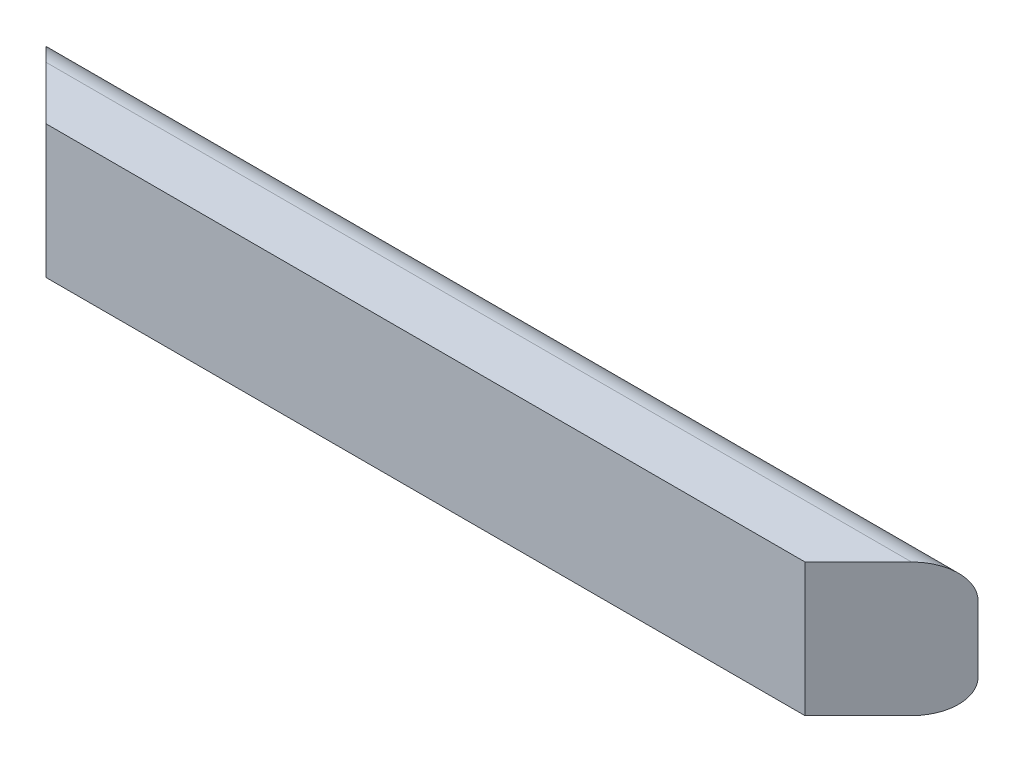
SolidWorks part; units mm, degrees
ref_plane "Front" through (0, 0, 0) normal (0, 0, 1) x (1, 0, 0)
ref_plane "Top" through (0, 0, 0) normal (0, 1, 0) x (1, 0, 0)
ref_plane "Right" through (0, 0, 0) normal (1, 0, 0) x (0, 0, -1)
sketch "Sketch1" plane through (0, 0, 0) normal (1, 0, 0) x (0, 0, -1)
  line L0 (0, 0) -> (0, 127) construction
  line L1 (0, 0) -> (31.75, 0)
  line L2 (31.75, 127) -> (0, 127)
  line L3 (63.5, 95.25) -> (63.5, 31.75)
  line L4 (0, 0) -> (-19.05, 0)
  line L5 (-19.05, 0) -> (-19.05, 127)
  line L6 (-19.05, 127) -> (0, 127)
  arc A0 (31.75, 0) -> (63.5, 31.75) centre (31.75, 31.75) ccw
  arc A1 (63.5, 95.25) -> (31.75, 127) centre (31.75, 95.25) ccw
  dimension "D2" = 63.5
  dimension "D1" = 19.05
extrude "Boss-Extrude1" add sketch "Sketch1" along normal blind 889
ref_plane "Mid_Plane" through (444.5, 0, 0) normal (1, 0, 0) x (0, 0, -1)
ref_plane "Plane1" through (412.75, 0, 412.75) normal (0.7071, 0, 0.7071) x (0, 1, 0)
sketch "Sketch2" plane through (412.75, 0, 412.75) normal (0.7071, 0, 0.7071) x (0, 1, 0)
  line L0 (31.75, -673.5192) -> (95.25, -673.5192) construction
  line L1 (205.1964, -283.2904) -> (-139.2061, -283.2904)
  line L2 (205.1964, -283.2904) -> (205.1964, -1063.748)
  line L3 (205.1964, -1063.748) -> (-139.2061, -1063.748)
  line L4 (-139.2061, -283.2904) -> (-139.2061, -1063.748)
  line L5 (205.1964, -283.2904) -> (-139.2061, -1063.748) construction
  line L6 (205.1964, -1063.748) -> (-139.2061, -283.2904) construction
  point P4 (32.9952, -673.5192)
extrude "Cut-Extrude1" cut sketch "Sketch2" along normal through all
mirror "Mirror1" about plane through (444.5, 0, 0) normal (1, 0, 0) of "Cut-Extrude1"
